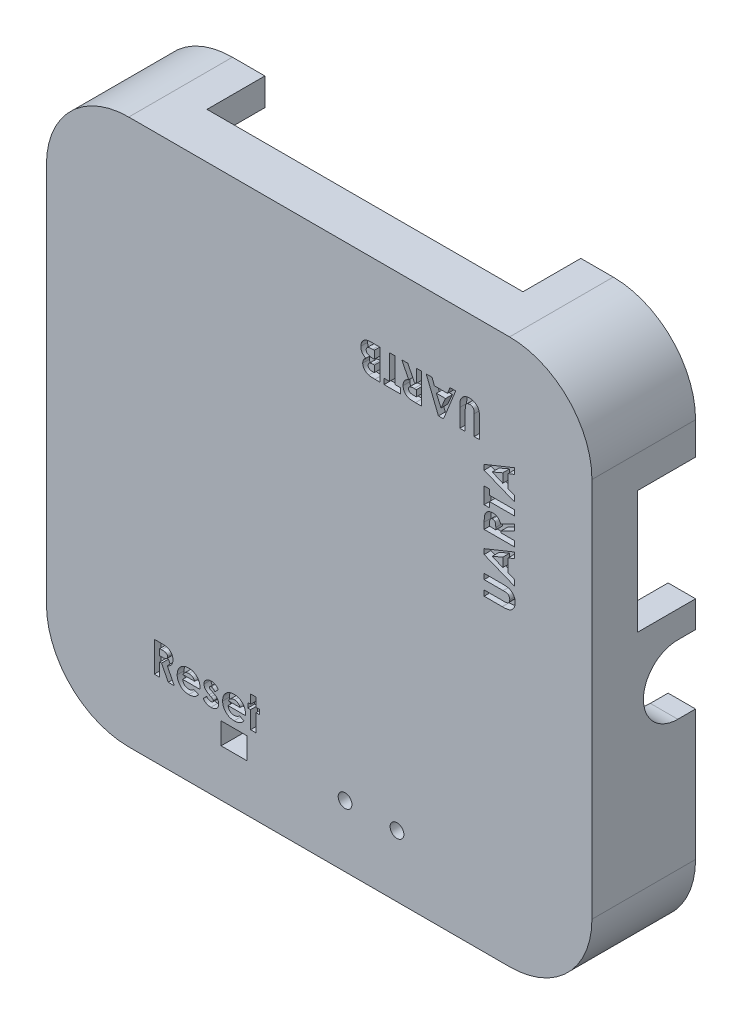
SolidWorks part; units mm, degrees
material "ABS"
ref_plane "Front Plane" through (0, 0, 0) normal (0, 0, 1) x (1, 0, 0)
ref_plane "Top Plane" through (0, 0, 0) normal (0, 1, 0) x (1, 0, 0)
ref_plane "Right Plane" through (0, 0, 0) normal (1, 0, 0) x (0, 0, -1)
sketch "Sketch1" plane through (0, 0, 0) normal (0, 0, 1) x (1, 0, 0)
  line L0 (22, 31.5165) -> (-22, 31.5165)
  line L1 (-31.5165, 22) -> (-31.5165, -22)
  line L2 (-22, -31.5165) -> (22, -31.5165)
  line L3 (31.5165, -22) -> (31.5165, 22)
  line L8 (-28.3415, 22) -> (-28.3415, -22)
  line L9 (-22, -28.3415) -> (22, -28.3415)
  line L10 (28.3415, -22) -> (28.3415, 22)
  line L11 (22, 28.3415) -> (-22, 28.3415)
  line L12 (-28.3415, 22) -> (-28.3415, -22)
  line L13 (-22, -28.3415) -> (22, -28.3415)
  line L14 (28.3415, -22) -> (28.3415, 22)
  line L15 (22, 28.3415) -> (-22, 28.3415)
  arc A0 (-22, 31.5165) -> (-31.5165, 22) centre (-22, 22) ccw
  arc A1 (-31.5165, -22) -> (-22, -31.5165) centre (-22, -22) ccw
  arc A2 (22, -31.5165) -> (31.5165, -22) centre (22, -22) ccw
  arc A3 (31.5165, 22) -> (22, 31.5165) centre (22, 22) ccw
  arc A8 (-22, 28.3415) -> (-28.3415, 22) centre (-22, 22) ccw
  arc A9 (-28.3415, -22) -> (-22, -28.3415) centre (-22, -22) ccw
  arc A10 (22, -28.3415) -> (28.3415, -22) centre (22, -22) ccw
  arc A11 (28.3415, 22) -> (22, 28.3415) centre (22, 22) ccw
  arc A12 (-22, 28.3415) -> (-28.3415, 22) centre (-22, 22) ccw
  arc A13 (-28.3415, -22) -> (-22, -28.3415) centre (-22, -22) ccw
  arc A14 (22, -28.3415) -> (28.3415, -22) centre (22, -22) ccw
  arc A15 (28.3415, 22) -> (22, 28.3415) centre (22, 22) ccw
  dimension "D1" = 1.8415
  dimension "D2" = 3.175
extrude "Boss-Extrude1" add sketch "Sketch1" along normal blind 3.175 contours A1 L2 A2 L3 A3 L0 A0 L1
ref_plane "Plane1" through (-31.5165, -22, 0) normal (0, -1, 0) x (-1, 0, 0)
extrude "Boss-Extrude2" add sketch "Sketch1<3>" against normal up to surface (8.8 mm away)
sketch "Sketch1<3>" plane through (0, 0, 0) normal (0, 0, 1) x (1, 0, 0) same geometry as "Sketch1"
sketch "Sketch3" plane through (31.5165, 0, 0) normal (1, 0, 0) x (0, 0, -1)
  line L0 (6.745, -6.9447) -> (8.8, -6.9447)
  line L1 (8.8, -22) -> (8.8, 22) construction
  line L2 (8.8, -6.9447) -> (8.8, -6.3713)
  line L3 (6.745, -2.976) -> (2.7763, -2.976) construction
  line L4 (8.8, 0.9928) -> (8.8, 0.4193)
  line L5 (6.745, 0.9928) -> (8.8, 0.9928)
  line L6 (8.8, -6.3713) -> (8.8, 0.4193)
  line L7 (3.7, 7.97) -> (3.7, 14.37) construction
  line L8 (5.1, 16.67) -> (6.1, 16.67) construction
  line L9 (6.1, 5.67) -> (5.1, 5.67) construction
  line L16 (6.1, 5.67) -> (5.1, 5.67) construction
  line L17 (5.1, 16.67) -> (6.1, 16.67) construction
  line L18 (3.7, 7.97) -> (3.7, 14.37) construction
  line L19 (8.8, 4.0825) -> (2.1125, 4.0825)
  line L20 (2.1125, 18.2575) -> (8.8, 18.2575)
  line L21 (2.1125, 4.0825) -> (2.1125, 18.2575)
  line L22 (8.8, 4.0825) -> (8.8, 18.2575)
  line L23 (8.8, -11.003) -> (8.8, 10.997) construction
  line L24 (8.8, -22) -> (8.8, 22) construction
  line L25 (6.1, 4.0825) -> (5.1, 4.0825) construction
  line L26 (5.1, 18.2575) -> (6.1, 18.2575) construction
  circle A3 centre (6.745, -2.976) radius 3.9687
  arc A4 (6.745, 0.9928) -> (6.745, -6.9447) centre (6.745, -2.976) ccw
  dimension "D3" = 1.5875
  dimension "D1" = 0.7937
  dimension "D2" = 1.5875
extrude "Cut-Extrude1" cut sketch "Sketch3" against normal up to next
sketch "Sketch5" plane through (0, 31.5165, 0) normal (0, 1, 0) x (1, 0, 0)
  line L0 (0.789, 3.7) -> (-14.361, 3.7) construction
  line L1 (-16.661, 5.1) -> (-16.661, 6.1) construction
  line L2 (16.67, 6.1) -> (16.67, 5.1) construction
  line L3 (16.67, 6.1) -> (16.67, 5.1) construction
  line L4 (-16.661, 5.1) -> (-16.661, 6.1) construction
  line L5 (0.789, 3.7) -> (-14.361, 3.7) construction
  line L6 (18.2575, 8.8) -> (18.2575, 2.1125)
  line L7 (-18.2485, 2.1125) -> (-18.2485, 8.8)
  line L8 (14.37, 3.7) -> (7.97, 3.7) construction
  line L9 (18.2575, 8.8) -> (-18.2485, 8.8)
  line L10 (22, 8.8) -> (-22, 8.8) construction
  line L11 (18.2575, 6.1) -> (18.2575, 5.1) construction
  line L12 (-18.2485, 5.1) -> (-18.2485, 6.1) construction
  line L13 (-18.2485, 2.1125) -> (18.2575, 2.1125)
  dimension "D2" = 1.5875
  dimension "D1" = 1.5875
extrude "Cut-Extrude2" cut sketch "Sketch5" against normal blind 3.175
sketch "Sketch6" plane through (-31.5165, 0, 0) normal (-1, 0, 0) x (0, 0, 1)
  line L3 (-8.8, 22) -> (-8.8, -22) construction
  line L4 (-8.8, -2.253) -> (-2.196, -2.253)
  line L5 (-8.8, -2.253) -> (-8.8, -15.207)
  line L6 (-8.8, -15.207) -> (-2.196, -15.207)
  line L7 (-2.196, -2.253) -> (-2.196, -15.207)
  line L8 (-4.505, -8.73) -> (-7.6907, -8.73) construction
  line L9 (-4.505, -5.73) -> (-4.505, -11.73) construction
  dimension "D1" = 6.604
  dimension "D2" = 12.954
extrude "Cut-Extrude3" cut sketch "Sketch6" against normal blind 3.175
sketch "Sketch7" plane through (0, 0, 3.175) normal (0, 0, 1) x (1, 0, 0)
  line L4 (-8.33, -23.57) -> (-11.33, -23.57)
  line L5 (-11.33, -23.57) -> (-11.33, -26.07)
  line L6 (-11.33, -26.07) -> (-8.33, -26.07)
  line L7 (-8.33, -26.07) -> (-8.33, -23.57)
  line L8 (-8.33, -23.57) -> (-11.33, -23.57)
  line L9 (-11.33, -23.57) -> (-11.33, -26.07)
  line L10 (-11.33, -26.07) -> (-8.33, -26.07)
  line L11 (-8.33, -26.07) -> (-8.33, -23.57)
  circle A0 centre (2.99, -24.39) radius 0.7938
  circle A1 centre (8.99, -24.39) radius 0.7937
  dimension "D2" = 1.5875
  dimension "D1" = 0
extrude "Cut-Extrude4" cut sketch "Sketch7" against normal blind 3.175
sketch "Sketch8" plane through (0, 0, 3.175) normal (0, 0, 1) x (1, 0, 0)
  line L0 (22.5586, 3.6929) -> (22.5586, 18.9329) construction
  line L1 (28.3415, -22) -> (28.3415, 22) construction
  line L2 (18.9405, 22.9963) -> (3.0655, 22.9963) construction
  text T0 "<b>Reset</b>"
  text T1 "<b>UARTA</b>"
  text T2 "<b>UARTB</b>"
  dimension "D1" = 15.24
  dimension "D2" = 15.875
  dimension "D3" = 270
extrude "Cut-Extrude5" cut sketch "Sketch8" against normal blind 0.7937
